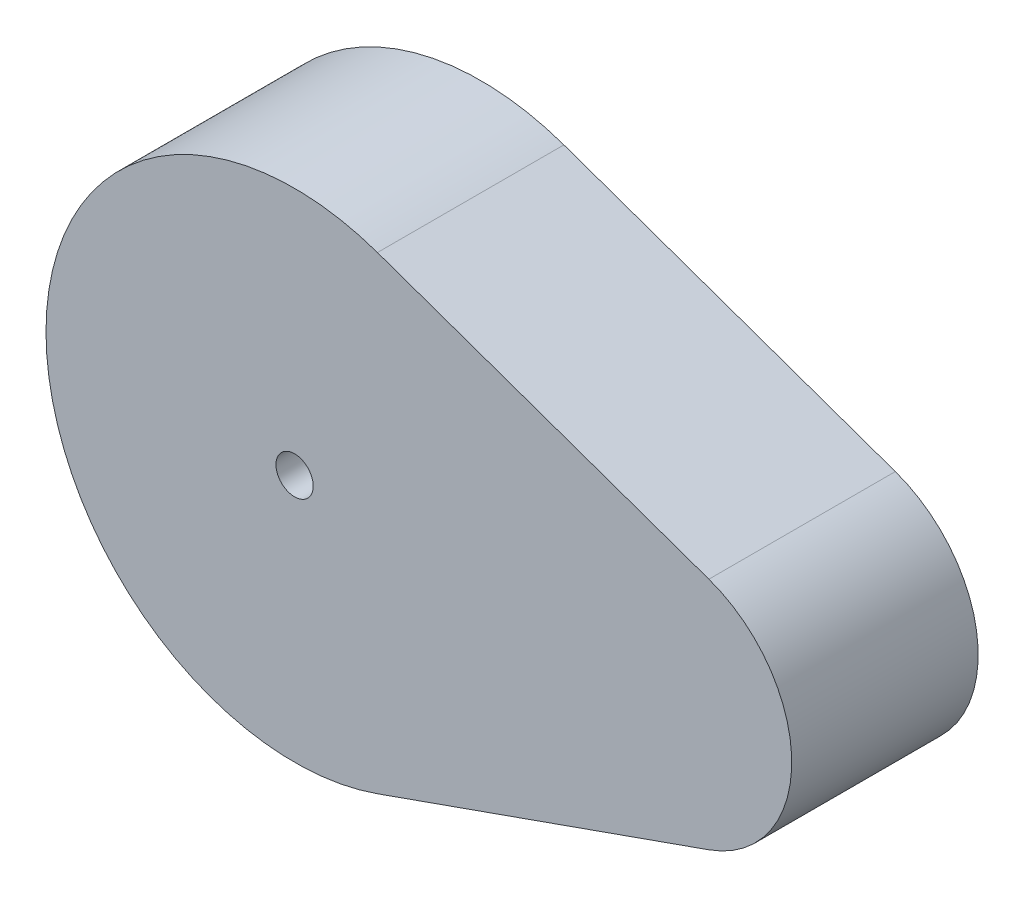
SolidWorks part; units mm, degrees
ref_plane "Front Plane" through (0, 0, 0) normal (0, 0, 1) x (1, 0, 0)
ref_plane "Top Plane" through (0, 0, 0) normal (0, 1, 0) x (1, 0, 0)
ref_plane "Right Plane" through (0, 0, 0) normal (1, 0, 0) x (0, 0, -1)
sketch "Sketch2" plane through (0, 0, 0) normal (0, 1, 0) x (1, 0, 0)
  line L0 (0, 0) -> (0, 6) construction
  dimension "D1" = 6
sketch "Sketch1" plane through (0, 0, 0) normal (0, 0, 1) x (1, 0, 0)
  line L0 (12, 0) -> (0, 0) construction
  line L5 (2.6667, 7.5425) -> (13.3333, 3.7712)
  line L6 (13.3333, -3.7712) -> (2.6667, -7.5425)
  circle A0 centre (0, 0) radius 0.6
  arc A1 (13.3333, 3.7712) -> (13.3333, -3.7712) centre (12, 0) cw
  arc A2 (2.6667, 7.5425) -> (2.6667, -7.5425) centre (0, 0) ccw
  point P10 (16, 0)
  dimension "D1" = 1.2
  dimension "D2" = 8
  dimension "D3" = 4
  dimension "D4" = 16
extrude "Boss-Extrude1" add sketch "Sketch1" against normal up to vertex (6 mm away) contours L5 A2 L6 A1 A0 up to point (0, 0, -6)
equation "\"t_wood\"= 6' Thickness of the wood"
equation "\"t_glass\"= 2.5'Thickness of glass panels"
equation "\"w_glass\"= 181"
equation "\"h_glass\"= 151"
equation "\"h_food_internal\" = 60"
equation "\"entry_height\"= 20"
equation "\"entry diameter\"= 8"
equation "\"glass_bottom_overlap\"= 8"
equation "\"default_finger_size\"= 12"
equation "\"brood_depth\"= 42"
equation "\"outer_box_depth\" = \"brood_depth\" + ( 2 * \"t_glass\" ) + ( 2 * \"t_wood\" )"
equation "\"outer_box_width\"= \"w_glass\" + ( 2 * \"t_wood\" )"
equation "\"food_top_clearance\"= 10"
equation "\"outer_box_height\"= \"t_wood\" + \"h_glass\" + \"t_wood\" + \"h_food_internal\" + \"food_top_clearance\" + \"t_wood\""
equation "\"food_internal_depth\"= \"brood_depth\" + \"t_glass\" + \"t_glass\" - \"t_wood\" - \"t_wood\""
equation "\"food_channel_clearance_width\"= 14"
equation "\"bar_top_play\"= 0.5"
equation "\"bar_entry_angle\"= 10"
equation "\"bar_width\"= 20"
equation "\"entry_disk_play\"= 0.3"
equation "\"D1@Sketch2\"=\"t_wood\""
